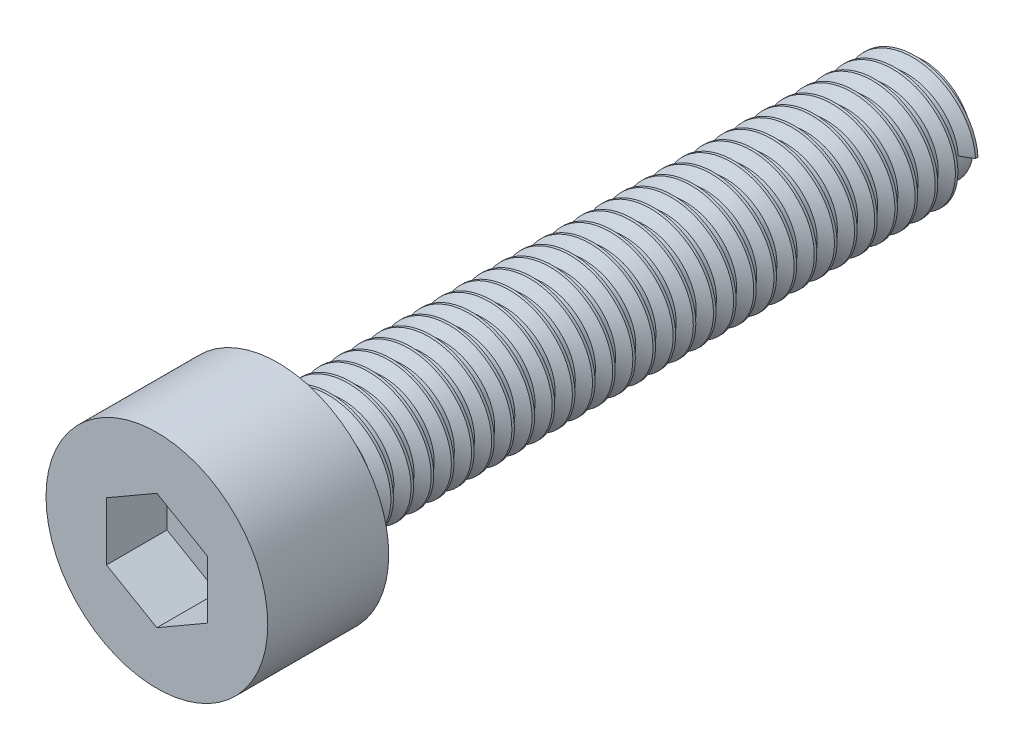
SolidWorks part; units mm, degrees
material "Cast Carbon Steel"
ref_plane "Front Plane" through (0, 0, 0) normal (0, 0, 1) x (1, 0, 0)
ref_plane "Top Plane" through (0, 0, 0) normal (0, 1, 0) x (1, 0, 0)
ref_plane "Right Plane" through (0, 0, 0) normal (1, 0, 0) x (0, 0, -1)
sketch "Sketch1" plane through (0, 0, 0) normal (0, 0, 1) x (1, 0, 0)
  circle A0 centre (0, 0) radius 2.75
  dimension "D1" = 5.5
extrude "Boss-Extrude1" add sketch "Sketch1" along normal blind 3
sketch "Sketch2" plane through (0, 0, 0) normal (0, 0, -1) x (-1, 0, 0)
  circle A0 centre (0, 0) radius 1.25
  dimension "D1" = 2.5
extrude "Boss-Extrude2" add sketch "Sketch2" along normal blind 16
sketch "Sketch3" plane through (0, 0, 3) normal (0, 0, 1) x (1, 0, 0)
  line L1 (0, 1.4434) -> (-1.25, 0.7217)
  line L2 (-1.25, 0.7217) -> (-1.25, -0.7217)
  line L3 (-1.25, -0.7217) -> (0, -1.4434)
  line L4 (0, -1.4434) -> (1.25, -0.7217)
  line L5 (1.25, -0.7217) -> (1.25, 0.7217)
  line L6 (1.25, 0.7217) -> (0, 1.4434)
  circle A0 centre (0, 0) radius 1.25 construction
  dimension "D1" = 2.5
extrude "Cut-Extrude1" cut sketch "Sketch3" against normal blind 1.5
thread "Thread1" pitch 0.5 method extrude profile "Thread Profile1" start angle 0, offset 0, length 16, pitch 0.5, diameter 2.5
ref_plane "Plane1" through (1.25, 0, -16) normal (0, -1, 0) x (1, 0, 0)
sketch "Thread Profile1" plane through (1.25, 0, -16) normal (0, -1, 0) x (1, 0, 0)
  line L0 (0, 0) -> (0, 0.5) construction
  line L1 (0, 0) -> (0.2706, 0.1562)
  line L2 (0.2706, 0.1562) -> (0.2706, 0.2187)
  line L3 (0.2706, 0.2187) -> (0, 0.375)
  line L4 (0.2706, 0.1875) -> (0, 0.1875) construction
  line L11 (0, 0) -> (0, 0.375)
  point P2 (0, 0)
  dimension "Pitch" = 0.5
  dimension "Profile_Angle" = 60
  dimension "Profile_Land" = 0.0625
  dimension "Profile_Height" = 0.2706
